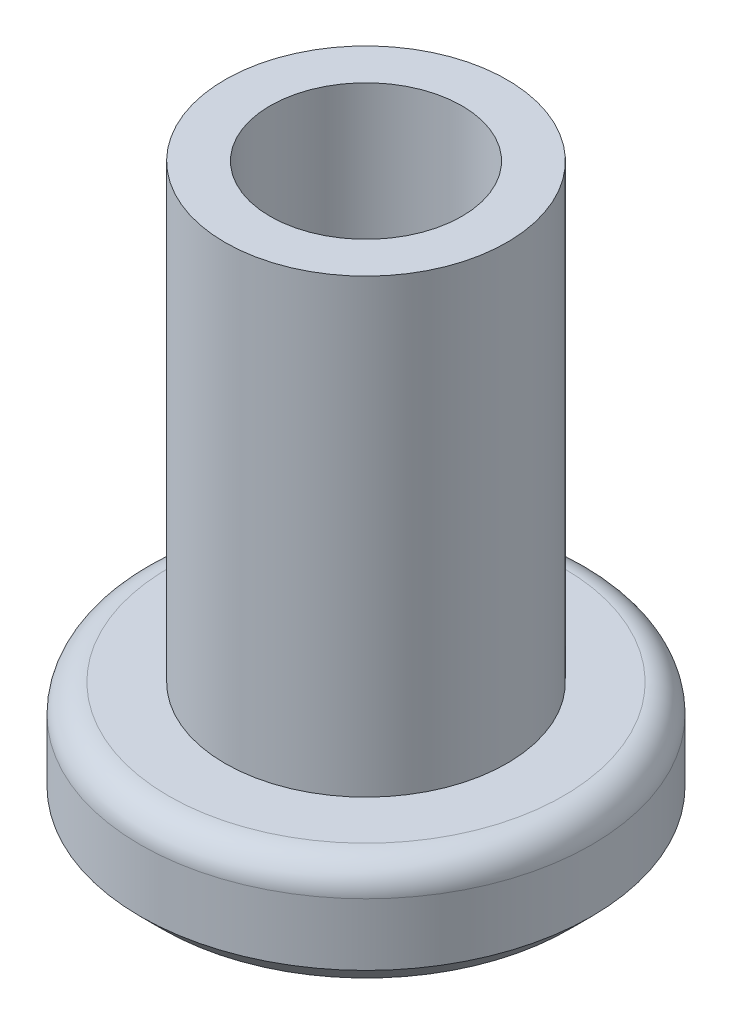
SolidWorks part; units mm, degrees
ref_plane "Front Plane" through (0, 0, 0) normal (0, 0, 1) x (1, 0, 0)
ref_plane "Top Plane" through (0, 0, 0) normal (0, 1, 0) x (1, 0, 0)
ref_plane "Right Plane" through (0, 0, 0) normal (1, 0, 0) x (0, 0, -1)
sketch "Sketch1" plane through (0, 0, 0) normal (0, 1, 0) x (1, 0, 0)
  circle A0 centre (0, 0) radius 1.7
  circle A1 centre (0, 0) radius 2.5
  circle A2 centre (0, 0) radius 4
  circle A3 centre (0, 0) radius 3
  dimension "D1" = 3.4
  dimension "D2" = 5
  dimension "D3" = 8
  dimension "D4" = 6
extrude "Boss-Extrude1" add sketch "Sketch1" along normal blind 8 contours A1 A0 region at (-2.4293, 0, 0)
extrude "Boss-Extrude2" add sketch "Sketch1<3>" against normal blind 2 contours A1 A0 | A3 A1 | A2 A3 region at (-2.4293, 0, 0) region at (-3.8869, 0, 0) region at (-2.9151, 0, 0)
sketch "Sketch1<3>" plane through (0, 0, 0) normal (0, 1, 0) x (1, 0, 0) same geometry as "Sketch1"
fillet "Fillet1" radius 0.5 1 edges at (0, 0, 4)
chamfer "Chamfer1" distance 0.4 angle 45 2 edges at (0, -2, 4) (0, -2, 1.7)
ref_point "Point1"
